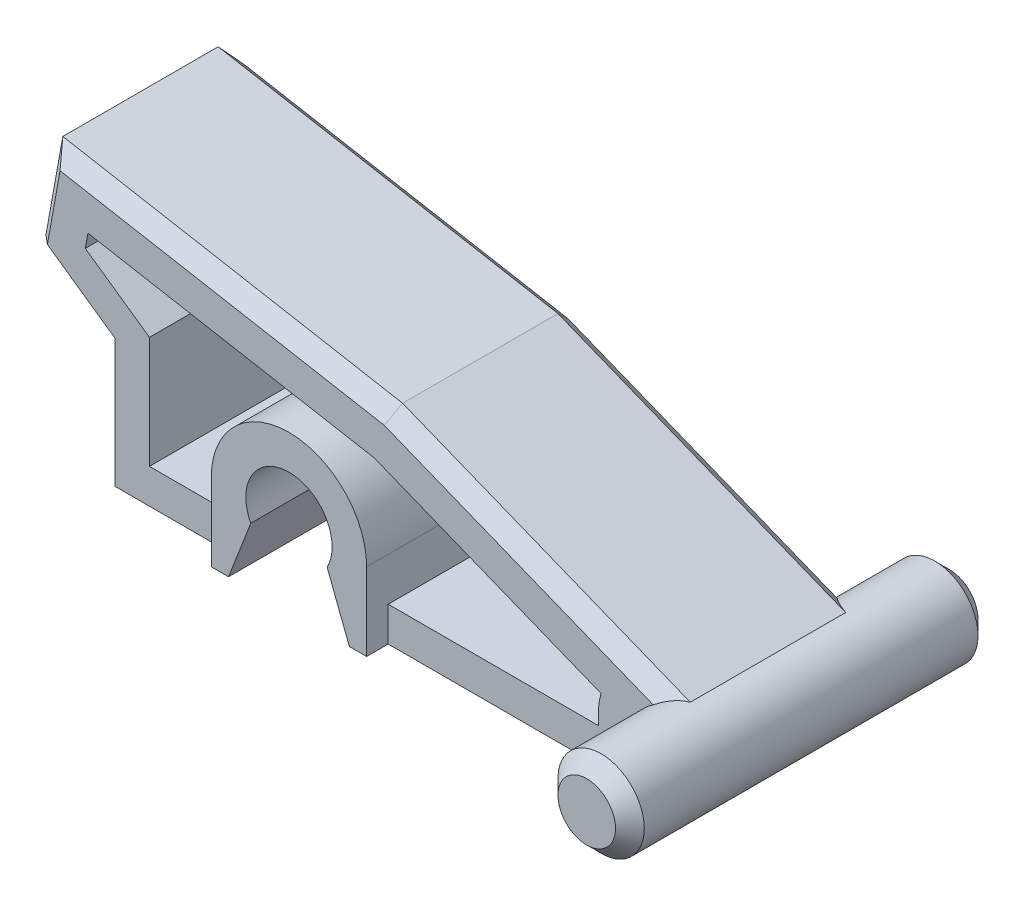
SolidWorks part; units mm, degrees
ref_plane "Front Plane" through (0, 0, 0) normal (0, 0, 1) x (1, 0, 0)
ref_plane "Top Plane" through (0, 0, 0) normal (0, 1, 0) x (1, 0, 0)
ref_plane "Right Plane" through (0, 0, 0) normal (1, 0, 0) x (0, 0, -1)
sketch "Sketch1" plane through (0, 0, 0) normal (0, 0, 1) x (1, 0, 0)
  line L0 (10, -4.4) -> (10, -1.4)
  line L1 (-10, -4.4) -> (10, -4.4)
  line L2 (-10, -4.4) -> (-10, 4.4)
  line L3 (-10, 4.4) -> (10, 4.4)
  line L4 (10, -4.4) -> (10, 4.4)
  line L5 (-10, -4.4) -> (10, 4.4) construction
  line L6 (-10, 4.4) -> (10, -4.4) construction
  line L7 (10, -1.4) -> (0, 2.6)
  line L8 (0, 2.6) -> (-11.8102, 4.7258)
  line L9 (-11.8102, 4.7258) -> (-12.3948, 1.478)
  line L10 (-12.3948, 1.478) -> (-10, -0.2)
  point P0 (0, 0)
  dimension "D1" = 20
  dimension "D2" = 8.8
  dimension "D3" = 3
  dimension "D4" = 7
  dimension "D5" = 10
  dimension "D6" = 12
  dimension "D7" = 3.3
  dimension "D8" = 4.2
extrude "Boss-Extrude1" add sketch "Sketch1" along normal mid plane 6.4 contours L7 L8 L2 L1 L0 | L9 L10 L2 L8 region at (-1.4987, -0.9499, 0) region at (-11.0126, 2.476, 0)
sketch "Sketch2" plane through (0, 0, 3.2) normal (0, 0, 1) x (1, 0, 0)
  line L0 (-10, -4.4) -> (10, -4.4) construction
  line L1 (-10, -4.4) -> (-10, -0.2) construction
  line L2 (-5.4, -1.7) -> (-5.4, -4.4)
  line L3 (-5.4, -4.4) -> (-2.7, -4.4)
  line L4 (-2.7, -4.4) -> (-5.4, -1.7)
  line L5 (-2.7, -4.4) -> (0, -4.4)
  line L6 (0, -4.4) -> (0, -1.7)
  line L7 (0, -1.7) -> (-2.7, -4.4)
  circle A0 centre (-2.7, -1.7) radius 2.7
  line M13 (-10, -4.4) -> (10, -4.4)
  dimension "D1" = 5.4
  dimension "D2" = 7.3
extrude "Boss-Extrude2" add sketch "Sketch2" along normal mid plane 1.5 contours L7 A0 L4 | L4 A0 | L7 A0 | A0 L6 M13 | A0 L2 M13 region at (-4.7969, -3.7969, 3.2) region at (-2.7, -1.3499, 3.2) region at (-4.2767, -3.2767, 3.2) region at (-0.6031, -3.7969, 3.2) region at (-1.1233, -3.2767, 3.2)
mirror "Mirror1" about plane through (0, 0, 0) normal (0, 0, 1) of "Boss-Extrude2"
sketch "Sketch3" plane through (0, 0, 3.95) normal (0, 0, 1) x (1, 0, 0)
  line L0 (-4.8, -4.4) -> (-0.6, -4.4)
  line L1 (-5.4, -4.4) -> (0, -4.4) construction
  line L2 (-4.8, -4.4) -> (-4.0266, -2.4)
  line L3 (-4.0266, -2.4) -> (-1.3734, -2.4)
  line L4 (-1.3734, -2.4) -> (-0.6, -4.4)
  circle A0 centre (-2.7, -1.7) radius 1.5
  point P8 (-2.7, -4.4)
  line M5 (-5.4, -4.4) -> (0, -4.4)
  dimension "D1" = 3
  dimension "D2" = 4.2
  dimension "D3" = 0
  dimension "D4" = 2
extrude "Cut-Extrude1" cut sketch "Sketch3" against normal through all both and the other way through all contours L3 A0 | A0 L2 L4 M5 | L4 L0 L2 L3 region at (-2.7, -3.6868, 3.95) region at (-2.7, -1.4198, 3.95)
sketch "Sketch4" plane through (0, 0, 0) normal (0, 0, 1) x (1, 0, 0)
  line L0 (10, -4.4) -> (10, -1.4) construction
  circle A0 centre (10, -2.9) radius 1.5
extrude "Boss-Extrude3" add sketch "Sketch4" along normal mid plane 12.6
chamfer "Chamfer1" distance 0.5 angle 45 2 edges at (11.5, -2.9, -6.3) (11.5, -2.9, 6.3)
chamfer "Chamfer2" distance 0.5 angle 45 10 edges at (-10, -2.3, 3.2) (-11.1974, 0.639, 3.2) (-12.1025, 3.1019, 3.2) (-5.9051, 3.6629, 3.2) (5, 0.6, 3.2) (-10, -2.3, -3.2) (-11.1974, 0.639, -3.2) (-12.1025, 3.1019, -3.2) (-5.9051, 3.6629, -3.2) (5, 0.6, -3.2)
sketch "Sketch5" plane through (0, 0, 3.2) normal (0, 0, 1) x (1, 0, 0)
  line L0 (-10.5291, 2.2466) -> (-10.4382, 2.7516)
  line L1 (-10.4382, 2.7516) -> (-0.4711, 0.9575)
  line L2 (-0.4711, 0.9575) -> (7.3953, -2.1891)
  line L3 (7.3167, -3.2) -> (0, -3.2)
  line L4 (0, -1.7) -> (0, -4.4) construction
  line L5 (-10.5291, 2.2466) -> (-8.3, 0.6846)
  line L6 (-8.3, 0.6846) -> (-8.3, -3.2)
  line L7 (-8.3, -3.2) -> (-5.4, -3.2)
  line L8 (-5.4, -4.4) -> (-5.4, -1.7) construction
  line L9 (-11.4067, 4.1452) -> (-11.8461, 1.7041) construction
  line L10 (-0.1386, 2.1169) -> (-11.4067, 4.1452) construction
  line L11 (9.2123, -1.6234) -> (-0.1386, 2.1169) construction
  line L12 (0, -4.4) -> (10, -4.4) construction
  line L15 (-9.5, -4.4) -> (-5.4, -4.4) construction
  line L16 (-9.5, 0.0602) -> (-9.5, -4.4) construction
  line L17 (-11.8461, 1.7041) -> (-9.5, 0.0602) construction
  line L18 (-5.4, -3.2) -> (-5.4, -1.7)
  line L19 (0, -3.2) -> (0, -1.7)
  circle A0 centre (10, -2.9) radius 2.7
  circle A1 centre (10, -2.9) radius 1.5 construction
  circle A2 centre (-2.7, -1.7) radius 2.7
  line M14 (-5.4, -4.4) -> (-5.4, -1.7)
  arc M15 (-5.4, -1.7) -> (0, -1.7) centre (-2.7, -1.7) cw
  line M16 (0, -1.7) -> (0, -4.4)
  dimension "D4" = 1.2
  dimension "D9" = 5.4
  dimension "D1" = 1.2
  dimension "D2" = 1.2
  dimension "D3" = 1.2
  dimension "D5" = 1.2
  dimension "D6" = 1.2
  dimension "D7" = 1.2
  dimension "D8" = 1.2
extrude "Cut-Extrude2" cut sketch "Sketch5" against normal offset from surface (5.2 mm away) 1.2 contours A0 L2 L1 L0 L5 L6 L7 L3 M14 M15 M16 region at (-10.2978, 2.4656, 3.2) up to face at (-3.1844, -1.1086, -3.2)
